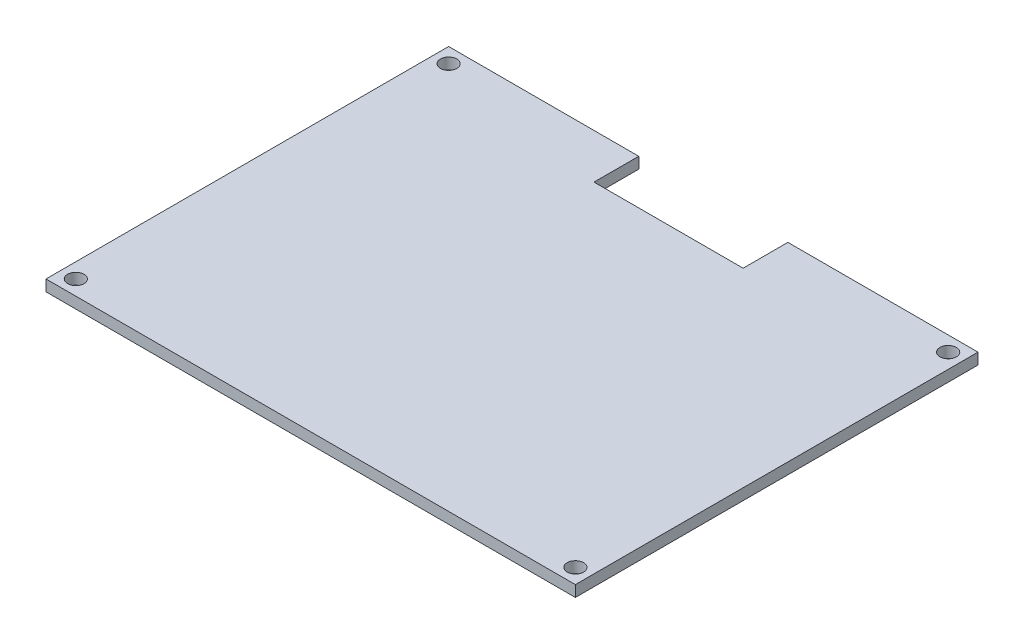
SolidWorks part; units mm, degrees
ref_plane "Front Plane" through (0, 0, 0) normal (0, 0, 1) x (1, 0, 0)
ref_plane "Top Plane" through (0, 0, 0) normal (0, 1, 0) x (1, 0, 0)
ref_plane "Right Plane" through (0, 0, 0) normal (1, 0, 0) x (0, 0, -1)
sketch "Sketch1" plane through (0, 0, 0) normal (0, 1, 0) x (1, 0, 0)
  line L1 (0, 0) -> (71, 0)
  line L2 (0, 0) -> (0, 54)
  line L3 (0, 54) -> (71, 54)
  line L4 (71, 0) -> (71, 54)
  dimension "D1" = 71
  dimension "D2" = 54
extrude "Boss-Extrude1" add sketch "Sketch1" along normal blind 1.5
sketch "Sketch2" plane through (0, 1.5, 0) normal (0, 1, 0) x (1, 0, 0)
  line L1 (25.5, 54) -> (45.5, 54)
  line L2 (25.5, 54) -> (25.5, 48)
  line L3 (25.5, 48) -> (45.5, 48)
  line L4 (45.5, 54) -> (45.5, 48)
  line L6 (71, 54) -> (0, 54) construction
  point P4 (35.5, 54)
  dimension "D1" = 20
  dimension "D2" = 6
extrude "Cut-Extrude1" cut sketch "Sketch2" against normal up to surface (1.5 mm away) up to face at (35.5, 0, -27)
sketch "Sketch5" plane through (0, 1.5, 0) normal (0, 1, 0) x (1, 0, 0)
  line L0 (2, 52) -> (2, 54) construction
  line L1 (25.5, 54) -> (0, 54) construction
  line L2 (2, 54) -> (2, 52) construction
  line L3 (2, 52) -> (0, 52) construction
  line L4 (0, 54) -> (0, 0) construction
  line L5 (69, 52) -> (69, 54) construction
  line L6 (71, 54) -> (45.5, 54) construction
  line L7 (69, 52) -> (71, 52) construction
  line L8 (71, 0) -> (71, 54) construction
  circle A0 centre (2, 52) radius 1.1
  circle A1 centre (69, 52) radius 1.1
  dimension "D1" = 2.2
  dimension "D3" = 2
extrude "Cut-Extrude2" cut sketch "Sketch5" against normal up to surface (1.5 mm away) up to face at (35.5, 0, -39)
ref_plane "Plane1" through (0, 0, -27) normal (0, 0, 1) x (1, 0, 0)
mirror "Mirror1" about plane through (0, 0, -27) normal (0, 0, 1) of "Cut-Extrude2"
sketch "Sketch6" plane through (0, 1.5, 0) normal (0, 1, 0) x (1, 0, 0)
  line L0 (63, 38) -> (71, 38) construction
  line L1 (71, 0) -> (71, 54) construction
  line L2 (63, 54) -> (63, 38) construction
  line L3 (71, 54) -> (45.5, 54) construction
  line L4 (63, 38) -> (63, 27) construction
  line L5 (63, 27) -> (63, 16) construction
  line L6 (0, 54) -> (0, 0) construction
  line L7 (18.45, 11) -> (24.45, 11)
  line L8 (18.45, 11) -> (18.45, 5)
  line L9 (18.45, 5) -> (24.45, 5)
  line L10 (24.45, 11) -> (24.45, 5)
  line L11 (32.5, 11) -> (38.5, 11)
  line L12 (32.5, 11) -> (32.5, 5)
  line L13 (32.5, 5) -> (38.5, 5)
  line L14 (38.5, 11) -> (38.5, 5)
  line L15 (46.55, 11) -> (52.55, 11)
  line L16 (46.55, 11) -> (46.55, 5)
  line L17 (46.55, 5) -> (52.55, 5)
  line L18 (52.55, 11) -> (52.55, 5)
  line L19 (18.45, 8) -> (0, 8) construction
  line L20 (24.45, 8) -> (32.5, 8) construction
  line L21 (38.5, 8) -> (46.55, 8) construction
  line L22 (0, 0) -> (71, 0) construction
  line L23 (8, 54) -> (8, 38) construction
  line L24 (5.1, 30) -> (10.9, 30)
  line L25 (5.1, 30) -> (5.1, 18.4)
  line L26 (5.1, 18.4) -> (10.9, 18.4)
  line L27 (10.9, 30) -> (10.9, 18.4)
  line L28 (25.5, 54) -> (0, 54) construction
  line L29 (8, 38) -> (8, 30) construction
  circle A0 centre (63, 38) radius 2.5
  circle A1 centre (63, 27) radius 2.5
  circle A2 centre (63, 16) radius 2.5
  circle A3 centre (8, 38) radius 2.5
  dimension "D1" = 5
  dimension "D2" = 8
  dimension "D3" = 16
  dimension "D4" = 11
  dimension "D5" = 18.45
  dimension "D6" = 6
  dimension "D7" = 8.05
  dimension "D8" = 8
  dimension "D9" = 8
  dimension "D10" = 11.6
  dimension "D11" = 5.8
  dimension "D12" = 8
  dimension "D13" = 16
extrude "Cut-Extrude3" [suppressed] cut sketch "Sketch6" against normal up to surface (1.5 mm away) up to face at (2, 0, -3.1)
